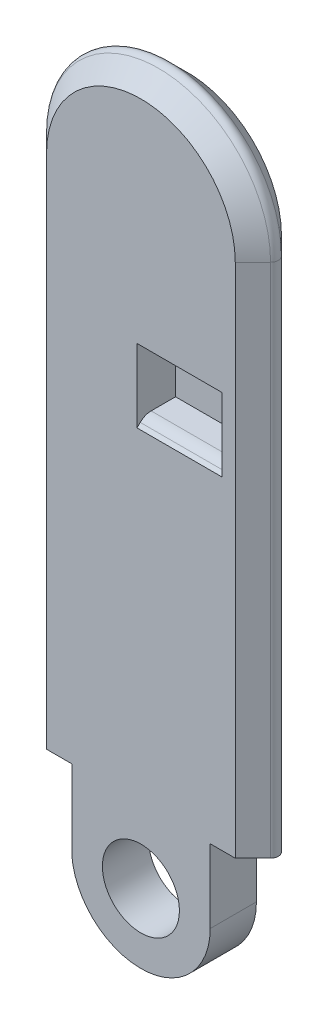
SolidWorks part; units mm, degrees
ref_plane "Płaszczyzna przednia" through (0, 0, 0) normal (0, 0, 1) x (1, 0, 0)
ref_plane "Płaszczyzna górna" through (0, 0, 0) normal (0, 1, 0) x (1, 0, 0)
ref_plane "Płaszczyzna prawa" through (0, 0, 0) normal (1, 0, 0) x (0, 0, -1)
sketch "Szkic1" plane through (0, 0, 0) normal (0, 0, 1) x (1, 0, 0)
  line L1 (-15.75, 33.5) -> (15.75, 33.5)
  line L2 (-15.75, 33.5) -> (-15.75, -33.5)
  line L3 (-15.75, -33.5) -> (15.75, -33.5)
  line L4 (15.75, 33.5) -> (15.75, -33.5)
  line L5 (-15.75, 33.5) -> (15.75, -33.5) construction
  line L6 (-15.75, -33.5) -> (15.75, 33.5) construction
  circle A0 centre (0, 33.5) radius 15.75
  point P0 (0, 0)
  dimension "D1" = 31.5
  dimension "D2" = 67
extrude "Dodanie-wyciągnięcie1" add sketch "Szkic1" against normal blind 6 contours L1 A0 | L1 A0 | A0 L2 L3 L4 region at (0, 40.1845, 0) region at (0, -6.0719, 0) region at (0, 26.8155, 0)
chamfer "Sfazowanie1" distance 3.5 angle 45 6 edges at (15.75, 0, -6) (0, 49.25, -6) (-15.75, 0, -6) (15.75, 0, 0) (0, 49.25, 0) (-15.75, 0, 0)
fillet "Zaokrąglenie1" radius 1 3 edges at (15.25, 0, -3) (0, 48.75, -3) (-15.25, 0, -3)
sketch "Szkic2" plane through (0, 0, 0) normal (0, 0, 1) x (1, 0, 0)
  line L0 (-0.5, 12.25) -> (10.5, 12.25) construction
  line L1 (-10.6279, -13.75) -> (-5.9102, -13.75) construction
  line L10 (-0.5, 15) -> (-0.5, 9.5)
  line L11 (10.5, 9.5) -> (10.5, 15)
  line L12 (-0.5, 15) -> (10.5, 15)
  line L13 (-0.5, 9.5) -> (10.5, 9.5)
  line L14 (5, 15) -> (5, 9.5) construction
  point P15 (-8.269, -13.75)
  dimension "D1" = 5.5
  dimension "D2" = 11
  dimension "D3" = 5
  dimension "D4" = 13.75
  dimension "D5" = 26
extrude "Wytnij-wyciągnięcie1" cut sketch "Szkic2" against normal blind 5
sketch "Szkic3" plane through (0, 0, -6) normal (0, 0, -1) x (-1, 0, 0)
  line L0 (6, -8.6458) -> (6, -1.9889) construction
  line L1 (1.5, -5.2389) -> (10.5, -5.2389)
  line L2 (6, -24.2101) -> (6, -27.9889) construction
  line L3 (1.5, -5.2389) -> (1.5, 1.2611)
  line L4 (1.5, -31.2389) -> (10.5, -31.2389)
  line L5 (1.5, -31.2389) -> (1.5, -24.7389)
  line L6 (1.5, -24.7389) -> (10.5, -24.7389)
  line L7 (10.5, -31.2389) -> (10.5, -24.7389)
  line L8 (1.5, -31.2389) -> (10.5, -24.7389) construction
  line L9 (1.5, -24.7389) -> (10.5, -31.2389) construction
  line L10 (1.5, 1.2611) -> (10.5, 1.2611)
  line L11 (10.5, -5.2389) -> (10.5, 1.2611)
  line L12 (1.5, -5.2389) -> (10.5, 1.2611) construction
  line L13 (1.5, 1.2611) -> (10.5, -5.2389) construction
  line L14 (6, -27.9889) -> (6, -1.9889) construction
  point P13 (10.3217, -15.2053)
  dimension "D1" = 24.7389
  dimension "D2" = 9
  dimension "D3" = 6.5
  dimension "D4" = 9
  dimension "D5" = 6.5
  dimension "D6" = 6
  dimension "D7" = 26
extrude "Wytnij-wyciągnięcie2" cut sketch "Szkic3" against normal blind 4.5
chamfer "Sfazowanie2" distance 0.5 angle 45 1 edges at (-6, -24.7389, -6)
sketch "Szkic4" plane through (0, 0, 0) normal (0, 0, 1) x (1, 0, 0)
  line L0 (0, -33.5) -> (0, -43.0308) construction
  line L1 (-12.25, -33.5) -> (12.25, -33.5) construction
  line L2 (9, -43.0308) -> (9, -33.5)
  line L3 (9, -33.5) -> (-8.9747, -33.5)
  line L4 (-8.9747, -33.5) -> (-8.9747, -43.7054)
  circle A0 centre (0, -43.0308) radius 5
  circle A1 centre (0, -43.0308) radius 9
  line M6 (-12.25, -33.5) -> (12.25, -33.5)
  dimension "D1" = 4
  dimension "D2" = 10
extrude "Dodanie-wyciągnięcie2" add sketch "Szkic4" against normal blind 6 contours L3 L0 A1 L2 | A1 A0 L4 | L0 L4 A1 M6 region at (6.4529, -35.5505, 0) region at (-6.4264, -35.5244, 0) region at (6.1841, -36.8467, 0)
sketch "Szkic5" plane through (0, 0, -6) normal (0, 0, -1) x (-1, 0, 0)
  line L3 (-5, 16) -> (0, 16)
  line L4 (0, 16) -> (0, -31)
  line L5 (-5, -31) -> (-5, 16)
  line L6 (-2.5, 16) -> (-2.5, -22.2858) construction
  line L8 (-0.5, 15) -> (-4.5, 15)
  line L9 (-0.5, 15) -> (-0.5, 9)
  line L10 (-0.5, 9) -> (-4.5, 9)
  line L11 (-4.5, 15) -> (-4.5, 9)
  line L12 (-0.5, 15) -> (-4.5, 9) construction
  line L13 (-0.5, 9) -> (-4.5, 15) construction
  point P6 (-2.5, 12)
  dimension "D1" = 1
  dimension "D2" = 0.5
  dimension "D3" = 6
  dimension "D4" = 5
  dimension "D5" = 16
  dimension "D6" = 2.5
extrude "Dodanie-wyciągnięcie3" add sketch "Szkic5" along normal blind 4.5 contours L8 L11 L10 L9 region at (2.5, 12, -6)
chamfer "Sfazowanie3" distance 3 angle 45 1 edges at (5, 15, 0)
chamfer "Sfazowanie4" distance 1 angle 45 1 edges at (5, 9.5, 0)
fillet "Zaokrąglenie2" radius 2 1 edges at (5, 9.5, -1)
